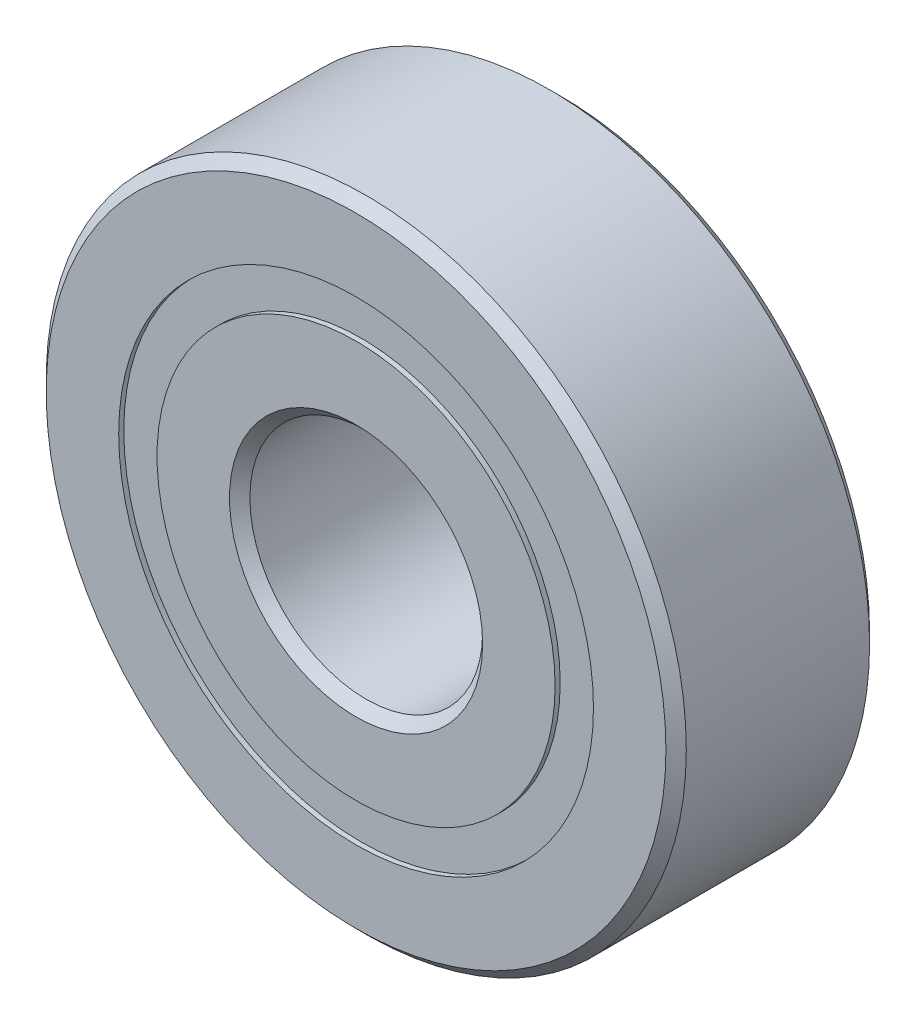
SolidWorks part; units mm, degrees
ref_plane "Front Plane" through (0, 0, 0) normal (0, 0, 1) x (1, 0, 0)
ref_plane "Top Plane" through (0, 0, 0) normal (0, 1, 0) x (1, 0, 0)
ref_plane "Right Plane" through (0, 0, 0) normal (1, 0, 0) x (0, 0, -1)
sketch "Sketch1" plane through (0, 0, 0) normal (1, 0, 0) x (0, 0, -1)
  line L0 (-3.5, 0) -> (3.5, 0) construction
  line L1 (0, 11) -> (0, -11) construction
  line L2 (3.15, 11) -> (-3.15, 11)
  line L3 (-3.15, 11) -> (-3.5, 10.65)
  line L4 (-3.5, 10.65) -> (-3.5, 8.1593)
  line L5 (-3.5, 8.1593) -> (-1.5556, 8.1593)
  line L6 (3.5, 8.1593) -> (1.5556, 8.1593)
  line L7 (3.5, 10.65) -> (3.5, 8.1593)
  line L8 (3.15, 11) -> (3.5, 10.65)
  line L9 (0, 11) -> (0, 7.5) construction
  line L10 (0, 7.5) -> (0, 4) construction
  arc A0 (-1.5556, 8.1593) -> (1.5556, 8.1593) centre (0, 7.5) cw
  point P14 (0, 4)
  dimension "Width" = 7
  dimension "OD" = 22
  dimension "D1" = 45
  dimension "D2" = 0.35
  dimension "Shaft Dia" = 8
  dimension "D3" = 3.1111
  dimension "D4" = 0.6593
revolve "Revolve1" add sketch "Sketch1" angle 360 about L0
sketch "Sketch3" plane through (0, 0, 0) normal (1, 0, 0) x (0, 0, -1)
  line L0 (-3.5, 6.8407) -> (-1.5556, 6.8407)
  line L1 (0, 11) -> (0, -11) construction
  line L2 (-3.5, 10.65) -> (-3.5, 8.1593) construction
  line L3 (-3.5, 6.8407) -> (-3.5, 4.35)
  line L4 (-3.15, 11) -> (-3.5, 10.65) construction
  line L5 (-3.5, 4.35) -> (-3.15, 4)
  line L6 (-3.15, 4) -> (3.15, 4)
  line L7 (3.15, 11) -> (3.15, -11) construction
  line L8 (3.15, 4) -> (3.5, 4.35)
  line L9 (3.5, -10.65) -> (3.5, 10.65) construction
  line L10 (3.5, 4.35) -> (3.5, 6.8407)
  line L11 (3.5, 6.8407) -> (1.5556, 6.8407)
  line L13 (3.15, 11) -> (3.5, 10.65) construction
  arc A0 (1.5556, 8.1593) -> (-1.5556, 8.1593) centre (0, 7.5) ccw construction
  arc A1 (1.5556, 6.8407) -> (-1.5556, 6.8407) centre (0, 7.5) cw
revolve "Revolve3" add sketch "Sketch3" angle 360 about L0
sketch "Sketch4" plane through (0, 0, 0) normal (1, 0, 0) x (0, 0, -1)
  line L0 (-1.6895, 7.5) -> (1.6895, 7.5)
  arc A2 (-1.6895, 7.5) -> (1.6895, 7.5) centre (0, 7.5) cw
  arc A3 (1.5556, 8.1593) -> (-1.5556, 8.1593) centre (0, 7.5) ccw construction
revolve "Revolve4" add sketch "Sketch4" angle 360 about L0
ref_axis "Axis1" through (0, 0, -3.5) along (0, 0, 1)
pattern_circular "CirPattern1" count 14 every 25.714 about axis through (0, 0, -3.5) along (0, 0, 1) of bodies 104
sketch "Sketch6" plane through (0, 0, 0) normal (1, 0, 0) x (0, 0, -1)
  line L0 (-3.5, 8.1593) -> (-1.5556, 8.1593) construction
  line L1 (-3.325, 8.1593) -> (-1.6895, 8.1593)
  line L2 (-3.325, 8.1593) -> (-3.325, 6.8407)
  line L3 (-3.325, 6.8407) -> (-1.6895, 6.8407)
  line L4 (-1.6895, 8.1593) -> (-1.6895, 6.8407)
  line L5 (-3.5, 6.8407) -> (-1.5556, 6.8407) construction
  line L6 (3.5, 8.1593) -> (1.5556, 8.1593) construction
  line L7 (3.325, 8.1593) -> (1.6895, 8.1593)
  line L8 (3.325, 8.1593) -> (3.325, 6.8407)
  line L9 (3.325, 6.8407) -> (1.6895, 6.8407)
  line L10 (1.6895, 8.1593) -> (1.6895, 6.8407)
  line L11 (3.5, 6.8407) -> (1.5556, 6.8407) construction
  line L12 (-3.15, 11) -> (-3.5, 10.65) construction
  point P18 (-3.325, 10.825)
revolve "Revolve5" add sketch "Sketch6" angle 360 about L0
equation "\"D2@Sketch1\" = \"Width@Sketch1\"*.05"
equation "\"D3@Sketch1\" = \"Width@Sketch1\"/2.25"
equation "\"D4@Sketch1\" = (((\"OD@Sketch1\"-\"Width@Sketch1\")/2)/3.25)/3.5"
equation "\"D2@CirPattern1\" = 360/\"Balls@CirPattern1\""
